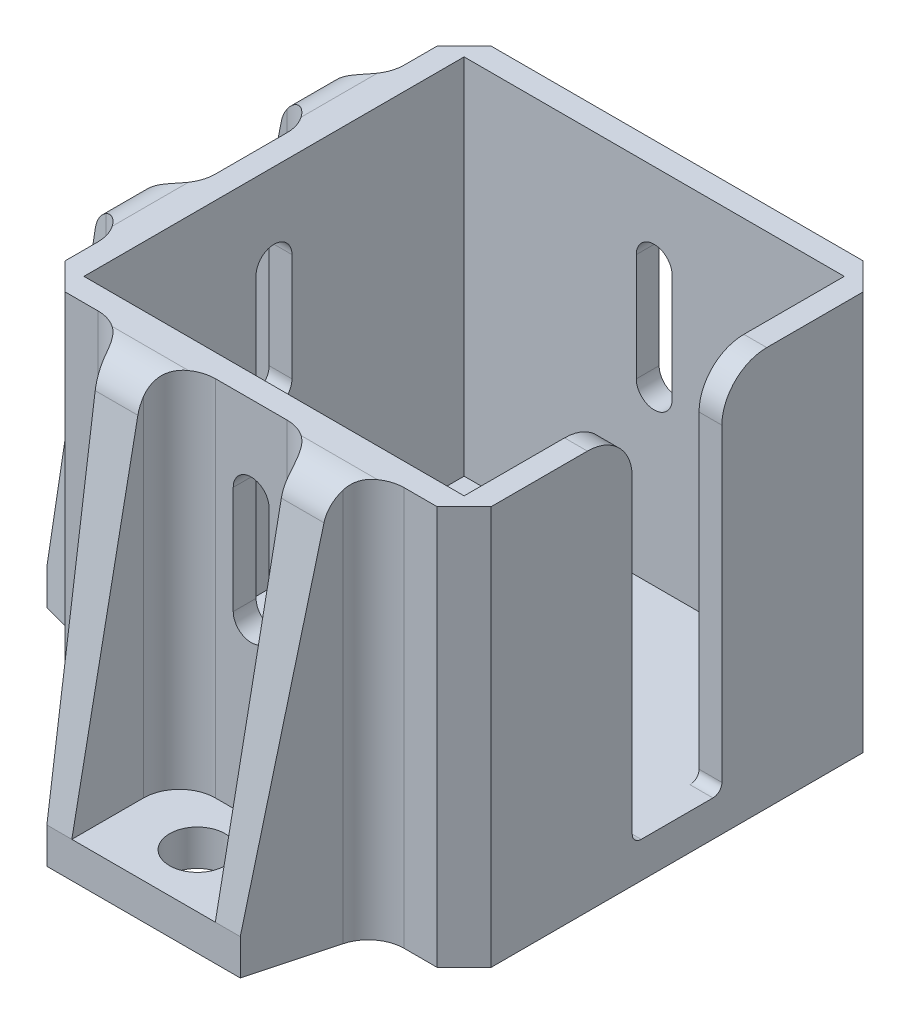
SolidWorks part; units mm, degrees
ref_plane "Front Plane" through (0, 0, 0) normal (0, 0, 1) x (1, 0, 0)
ref_plane "Top Plane" through (0, 0, 0) normal (0, 1, 0) x (1, 0, 0)
ref_plane "Right Plane" through (0, 0, 0) normal (1, 0, 0) x (0, 0, -1)
sketch "Sketch1" plane through (0, 0, 0) normal (0, 1, 0) x (1, 0, 0)
  line L1 (-21.2, -21.2) -> (21.2, -21.2)
  line L2 (-21.2, -21.2) -> (-21.2, 21.2)
  line L3 (-21.2, 21.2) -> (21.2, 21.2)
  line L4 (21.2, -21.2) -> (21.2, 21.2)
  line L5 (-21.2, -21.2) -> (21.2, 21.2) construction
  line L6 (-21.2, 21.2) -> (21.2, -21.2) construction
  line L7 (-23.75, -23.75) -> (23.75, -23.75)
  line L8 (-23.75, -23.75) -> (-23.75, 23.75)
  line L9 (-23.75, 23.75) -> (23.75, 23.75)
  line L10 (23.75, -23.75) -> (23.75, 23.75)
  line L11 (-23.75, -23.75) -> (23.75, 23.75) construction
  line L12 (-23.75, 23.75) -> (23.75, -23.75) construction
  point P0 (0, 0)
  point P6 (0, 0)
  dimension "D1" = 42.4
  dimension "D2" = 42.4
  dimension "D3" = 47.5
  dimension "D4" = 47.5
extrude "Boss-Extrude1" add sketch "Sketch1" along normal blind 40.5
fillet "Fillet1" radius 3 4 edges at (-23.75, 20.25, -23.75) (-23.75, 20.25, 23.75) (23.75, 20.25, -23.75) (23.75, 20.25, 23.75) profile chamfer
sketch "Sketch3" plane through (0, 0, 0) normal (0, 0, 1) x (1, 0, 0)
  line L0 (-23.75, 0) -> (-23.75, 40.5) construction
  line L1 (-23.75, 0) -> (-23.75, 40.5)
  line L3 (-35.75, 0) -> (-23.75, 0)
  line L4 (-23.75, 40.5) -> (-27.75, 40.5)
  line L5 (-27.75, 40.5) -> (-35.75, 0)
  dimension "D1" = 12
  dimension "D2" = 4
extrude "Boss-Extrude3" add sketch "Sketch3" along normal blind 10 and the other way blind 10
sketch "Sketch4" plane through (0, 0, 0) normal (0, 0, 1) x (1, 0, 0)
  line L3 (-35.75, 0) -> (-23.75, 0)
  line L4 (-23.75, 0) -> (-23.75, 40.5)
  line L5 (-23.75, 40.5) -> (-27.75, 40.5)
  line L6 (-35.75, 0) -> (-23.75, 0)
  line L7 (-23.75, 0) -> (-23.75, 40.5)
  line L10 (-23.75, 40.5) -> (-27.75, 40.5)
  line L11 (-27.75, 40.5) -> (-35.75, 0)
  line L12 (-27.75, 40.5) -> (-35.75, 0)
  dimension "D1" = 0
extrude "Cut-Extrude1" cut sketch "Sketch4" against normal blind 8 and the other way blind 8
sketch "Sketch7" plane through (0, 0, 0) normal (1, 0, 0) x (0, 0, -1)
  line L1 (-35.75, 0) -> (-23.75, 0)
  line L2 (-23.75, 0) -> (-23.75, 40.5)
  line L3 (-23.75, 40.5) -> (-27.75, 40.5)
  line L4 (-35.75, 0) -> (-27.75, 40.5)
  dimension "D1" = 12
  dimension "D2" = 4
extrude "Boss-Extrude4" add sketch "Sketch7" along normal blind 10 and the other way blind 10
sketch "Sketch8" plane through (0, 0, 0) normal (1, 0, 0) x (0, 0, -1)
  line L3 (-23.75, 0) -> (-23.75, 40.5)
  line L4 (-35.75, 0) -> (-23.75, 0)
  line L5 (-23.75, 40.5) -> (-27.75, 40.5)
  line L6 (-23.75, 0) -> (-23.75, 40.5)
  line L7 (-35.75, 0) -> (-23.75, 0)
  line L10 (-23.75, 40.5) -> (-27.75, 40.5)
  line L11 (-27.75, 40.5) -> (-35.75, 0)
  line L12 (-27.75, 40.5) -> (-35.75, 0)
  dimension "D1" = 0
extrude "Cut-Extrude2" cut sketch "Sketch8" against normal blind 8 and the other way blind 8
sketch "Sketch9" plane through (0, 0, 0) normal (0, 1, 0) x (1, 0, 0)
  line L0 (-35.75, 8) -> (-35.75, -8)
  line L1 (-8, -35.75) -> (8, -35.75)
  line L25 (-20.75, -23.75) -> (-10, -23.75)
  line L26 (-23.75, -10) -> (-23.75, -20.75)
  line L35 (20.75, 23.75) -> (-20.75, 23.75)
  line L36 (23.75, -20.75) -> (23.75, 20.75)
  line L38 (8, -23.75) -> (8, -35.75)
  line L39 (8, -23.75) -> (8, -35.75)
  line L45 (-20.75, -23.75) -> (-10, -23.75)
  line L46 (-23.75, -10) -> (-23.75, -20.75)
  line L55 (20.75, 23.75) -> (-20.75, 23.75)
  line L56 (23.75, -20.75) -> (23.75, 20.75)
  line L60 (-8, -23.75) -> (8, -23.75)
  line L61 (-8, -23.75) -> (8, -23.75)
  line L62 (-8, -35.75) -> (-8, -23.75)
  line L63 (-8, -35.75) -> (-8, -23.75)
  line L64 (-10, -23.75) -> (-10, -35.75)
  line L65 (-10, -23.75) -> (-10, -35.75)
  line L66 (-23.75, -20.75) -> (-20.75, -23.75)
  line L67 (-23.75, -20.75) -> (-20.75, -23.75)
  line L68 (-35.75, -10) -> (-23.75, -10)
  line L69 (-35.75, -10) -> (-23.75, -10)
  line L70 (-23.75, -8) -> (-35.75, -8)
  line L71 (-23.75, -8) -> (-35.75, -8)
  line L72 (-23.75, 8) -> (-23.75, -8)
  line L73 (-23.75, 8) -> (-23.75, -8)
  line L74 (-35.75, 8) -> (-23.75, 8)
  line L75 (-35.75, 8) -> (-23.75, 8)
  line L76 (-23.75, 10) -> (-35.75, 10)
  line L77 (-23.75, 10) -> (-35.75, 10)
  line L78 (-23.75, 20.75) -> (-23.75, 10)
  line L79 (-23.75, 20.75) -> (-23.75, 10)
  line L80 (-20.75, 23.75) -> (-23.75, 20.75)
  line L81 (-20.75, 23.75) -> (-23.75, 20.75)
  line L82 (23.75, 20.75) -> (20.75, 23.75)
  line L83 (23.75, 20.75) -> (20.75, 23.75)
  line L84 (20.75, -23.75) -> (23.75, -20.75)
  line L85 (20.75, -23.75) -> (23.75, -20.75)
  line L86 (10, -23.75) -> (20.75, -23.75)
  line L87 (10, -23.75) -> (20.75, -23.75)
  line L88 (10, -35.75) -> (10, -23.75)
  line L89 (10, -35.75) -> (10, -23.75)
  line L90 (-35.75, -8) -> (-35.75, -10)
  line L91 (-35.75, -8) -> (-35.75, -10)
  line L92 (-35.75, 10) -> (-35.75, 8)
  line L93 (-35.75, 10) -> (-35.75, 8)
  line L94 (8, -35.75) -> (10, -35.75)
  line L95 (8, -35.75) -> (10, -35.75)
  line L96 (-10, -35.75) -> (-8, -35.75)
  line L97 (-10, -35.75) -> (-8, -35.75)
  dimension "D1" = 0
extrude "Boss-Extrude6" add sketch "Sketch9" against normal blind 4 contours L87 L85 L56 L83 L55 L81 L79 L77 L75 L73 L71 L69 L46 L67 L45 L65 L63 L61 L39 L89 | L75 L0 L71 L73 | L63 L1 L39 L61 region at (-29.75, 0, 0) region at (-0.6118, 0, 0.6118) region at (0, 0, 29.75)
sketch "Sketch10" plane through (0, 0, 0) normal (0, 1, 0) x (1, 0, 0)
  line L1 (-23.75, -8) -> (-23.75, 8) construction
  circle A0 centre (-29.75, 0) radius 3.1
  dimension "D1" = 6.2
  dimension "D2" = 6
extrude "Cut-Extrude3" cut sketch "Sketch10" against normal through all
sketch "Sketch11" plane through (0, 0, 0) normal (0, 1, 0) x (1, 0, 0)
  line L0 (8, -23.75) -> (-8, -23.75) construction
  circle A0 centre (0, -29.75) radius 3.1
  dimension "D2" = 6.2
  dimension "D1" = 6
extrude "Cut-Extrude4" cut sketch "Sketch11" against normal through all
sketch "Sketch12" plane through (0, 0, -23.75) normal (0, 0, -1) x (-1, 0, 0)
  line L0 (-5, 0) -> (5, 0)
  line L2 (-5, 0) -> (-5, 40.5)
  line L3 (-20.75, 40.5) -> (20.75, 40.5) construction
  line L4 (-5, 40.5) -> (5, 40.5)
  line L5 (5, 40.5) -> (5, 0)
  point P6 (0, 0)
  dimension "D1" = 10
extrude "Cut-Extrude5" [suppressed] cut sketch "Sketch12" against normal up to surface (2.55 mm away)
fillet "Fillet6" [suppressed] radius 5
fillet "Fillet7" [suppressed] radius 1
sketch "Sketch14" plane through (23.75, 0, 0) normal (1, 0, 0) x (0, 0, -1)
  line L0 (-5, 40.5) -> (-5, 0)
  line L1 (-20.75, 40.5) -> (20.75, 40.5) construction
  line L2 (-21.2, 0) -> (21.2, 0) construction
  line L3 (-21.2, 0) -> (21.2, 0)
  line L4 (-20.75, 40.5) -> (20.75, 40.5)
  line L5 (5, 40.5) -> (5, 0)
  line L6 (0, 40.5) -> (0, 0) construction
  point P5 (0, 40.5)
  line M7 (20.75, 40.5) -> (-20.75, 40.5)
  dimension "D1" = 10
  dimension "D2" = 5
extrude "Cut-Extrude6" cut sketch "Sketch14" against normal blind 10 contours L6 L0 L3 M7 | L4 L6 L3 L5 region at (23.75, 20.25, 2.5) region at (23.75, 20.25, -2.5)
fillet "Fillet9" radius 5 2 edges at (22.475, 40.5, -5) (22.475, 40.5, 5)
fillet "Fillet10" radius 1 2 edges at (22.475, 0, -5) (22.475, 0, 5)
sketch "Sketch15" plane through (-23.75, 0, 0) normal (-1, 0, 0) x (0, 0, 1)
  line L0 (0, 19) -> (0, 31) construction
  line L1 (-2, 19) -> (-2, 31)
  line L2 (2, 19) -> (2, 31)
  arc A0 (-2, 19) -> (2, 19) centre (0, 19) ccw
  arc A1 (2, 31) -> (-2, 31) centre (0, 31) ccw
  point P3 (0, 25)
  dimension "D1" = 2
  dimension "D2" = 12
  dimension "D3" = 25
extrude "Cut-Extrude7" cut sketch "Sketch15" against normal up to surface (2.55 mm away) up to face at (-21.2, 20.25, 0)
sketch "Sketch16" plane through (0, 0, 23.75) normal (0, 0, 1) x (1, 0, 0)
  line L0 (0, 31) -> (0, 19) construction
  line L1 (2, 31) -> (2, 19)
  line L2 (-2, 31) -> (-2, 19)
  arc A0 (2, 31) -> (-2, 31) centre (0, 31) ccw
  arc A1 (-2, 19) -> (2, 19) centre (0, 19) ccw
  point P3 (0, 25)
  dimension "D1" = 2
  dimension "D2" = 12
  dimension "D3" = 25
extrude "Cut-Extrude8" cut sketch "Sketch16" against normal through all
fillet "Fillet14" [suppressed] radius 4
fillet "Fillet15" [suppressed] radius 4
chamfer "Chamfer1" distance 4 angle 75 2 edges at (10, 18.25, 23.75) (-23.75, 18.25, 10) first distance on face at (15.375, 18.25, 23.75) first distance on face at (-23.75, 18.25, 15.375)
chamfer "Chamfer2" distance 4 angle 75 1 edges at (-23.75, 18.25, -10) first distance on face at (-23.75, 18.25, -15.375)
chamfer "Chamfer3" distance 4 angle 75 1 edges at (-10, 18.25, 23.75) first distance on face at (-15.375, 18.25, 23.75)
fillet "Fillet16" radius 4 8 edges at (14, 18.25, 23.75) (8, 20.25, 23.75) (-8, 20.25, 23.75) (-14, 18.25, 23.75) (-23.75, 18.25, 14) (-23.75, 20.25, 8) (-23.75, 18.25, -14) (-23.75, 20.25, -8)
fillet "Fillet17" radius 4 4 edges at (-27.75, 40.5, -10.4641) (-27.75, 40.5, 10.4641) (-10.4641, 40.5, 27.75) (10.4641, 40.5, 27.75)
